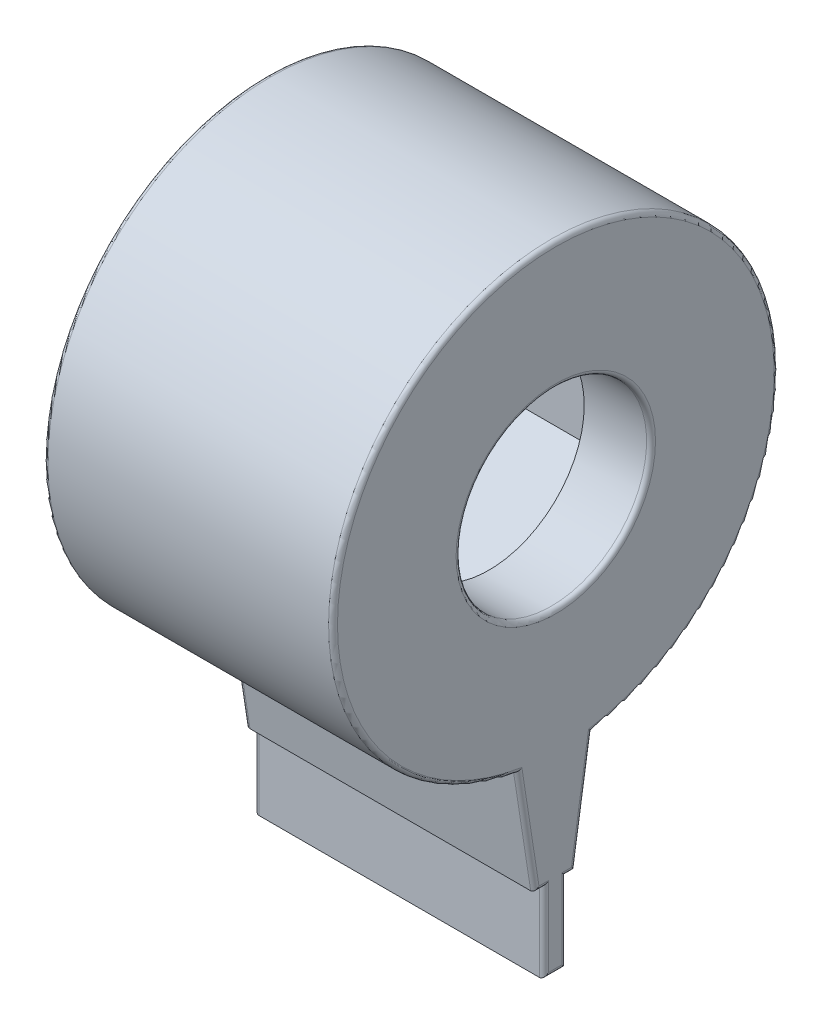
SolidWorks part; units mm, degrees
ref_plane "Front Plane" through (0, 0, 0) normal (0, 0, 1) x (1, 0, 0)
ref_plane "Top Plane" through (0, 0, 0) normal (0, 1, 0) x (1, 0, 0)
ref_plane "Right Plane" through (0, 0, 0) normal (1, 0, 0) x (0, 0, -1)
sketch "Sketch1" plane through (0, 0, 0) normal (1, 0, 0) x (0, 0, -1)
  line L0 (0, 0) -> (0, 13.6146) construction
  line L2 (-0.9, 5) -> (-1.9, 11.5)
  line L3 (-1.9, 11.5) -> (1.9, 11.5)
  line L4 (1.9, 11.5) -> (0.9, 5)
  line L6 (0.4986, 5) -> (0.4986, 1.4258)
  line L7 (0.4986, 1.4258) -> (-0.4986, 1.4258)
  line L8 (-0.4986, 1.4258) -> (-0.4986, 5)
  line L9 (-0.9, 5) -> (-0.4986, 5)
  line L10 (0.4986, 5) -> (0.9, 5)
  dimension "D1" = 11.5
  dimension "D2" = 0.9
  dimension "D3" = 0.9
  dimension "D4" = 1.9
  dimension "D5" = 1.9
  dimension "D6" = 6.5
extrude "Boss-Extrude1" add sketch "Sketch1" along normal blind 10 and the other way blind 3 contours L9 L8 L7 L6 L10 L4 L3 L2
sketch "Sketch3" plane through (0, 0, 0) normal (1, 0, 0) x (0, 0, -1)
  line L0 (-6.7656, 23.7554) -> (-6.7656, 15.9978)
  line L1 (-6.7656, 15.9978) -> (-0.0156, 12.1007)
  line L2 (-0.0156, 12.1007) -> (6.7449, 15.9795)
  line L3 (6.7449, 15.9795) -> (6.7449, 23.7737)
  line L4 (6.7449, 23.7737) -> (0.0267, 27.6524)
  line L5 (0.0267, 27.6524) -> (-6.7656, 23.7554)
  line L6 (0.0267, 27.6524) -> (0.0267, 2.6524) construction
  circle A0 centre (0.0267, 19.8766) radius 10
  dimension "D8" = 20
  dimension "D1" = 25
  dimension "D2" = 15.5518
  dimension "D3" = 7.7942
  dimension "D4" = 7.7576
  dimension "D5" = 7.8309
  dimension "D6" = 7.7575
  dimension "D7" = 7.7942
extrude "Boss-Extrude2" add sketch "Sketch3" along normal blind 7 separate body
sketch "Sketch4" plane through (7, 0, 0) normal (1, 0, 0) x (0, 0, -1)
  line L0 (0.0267, 27.6524) -> (0.0267, 24.1524) construction
  circle A0 centre (0.0267, 19.8766) radius 10
  circle A1 centre (0.0267, 19.8766) radius 4.2759
  dimension "D1" = 3.5
extrude "Boss-Extrude3" add sketch "Sketch4" along normal blind 3
sketch "Sketch5" plane through (0, 0, 0) normal (-1, 0, 0) x (0, 0, 1)
  circle A0 centre (-0.0267, 19.8766) radius 4.2759
  circle A1 centre (-0.0267, 19.8766) radius 10
extrude "Boss-Extrude5" add sketch "Sketch5" along normal blind 3
fillet "Fillet1" radius 0.2 18 edges at (10, 19.8766, -4.3026) (10, 5, -0.6993) (10, 3.2129, -0.4986) (10, 1.4258, 0) (10, 3.2129, 0.4986) (10, 5, 0.6993) (10, 7.511, 1.2863) (10, 29.8765, -0.0546) (10, 7.5064, -1.2856) (-3, 19.8766, 4.2491) (-3, 5, 0.6993) (-3, 3.2129, 0.4986) (-3, 1.4258, 0) (-3, 3.2129, -0.4986) (-3, 5, -0.6993) (-3, 7.5064, -1.2856) (-3, 29.8765, -0.0546) (-3, 7.511, 1.2863)
combine bodies "Combine1" operation type add bodies to combine 104 108
